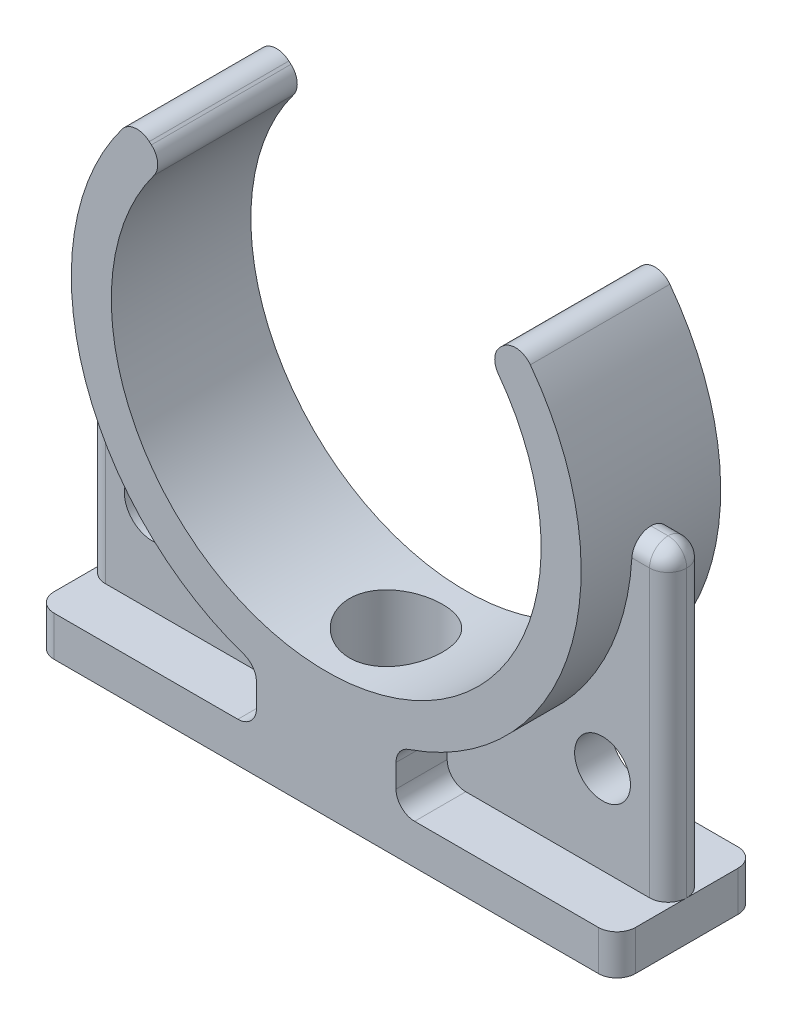
SolidWorks part; units mm, degrees
material "Delrin 2700 NC010, Low Viscosity Acetal Copolymer (SS)"
ref_plane "Front Plane" through (0, 0, 0) normal (0, 0, 1) x (1, 0, 0)
ref_plane "Top Plane" through (0, 0, 0) normal (0, 1, 0) x (1, 0, 0)
ref_plane "Right Plane" through (0, 0, 0) normal (1, 0, 0) x (0, 0, -1)
sketch "Sketch1" plane through (0, 0, 0) normal (0, 0, 1) x (1, 0, 0)
  line L0 (39.6875, 17.145) -> (39.6875, 0) construction
  line L1 (0, 0) -> (79.375, 0)
  line L2 (0, 0) -> (0, 46.99)
  line L3 (0, 46.99) -> (4.8932, 46.99)
  line L4 (79.375, 0) -> (79.375, 46.99)
  line L5 (0, 5.461) -> (30.1625, 5.461)
  line L6 (30.1625, 13.013) -> (30.1625, 5.461)
  line L7 (49.2125, 13.013) -> (49.2125, 5.461)
  line L8 (74.4818, 46.99) -> (79.375, 46.99)
  line L9 (49.2125, 5.461) -> (79.375, 5.461)
  line L10 (13.5513, 69.4559) -> (17.653, 65.8505)
  line L11 (65.8237, 69.4559) -> (61.722, 65.8505)
  circle A0 centre (8.9535, 17.526) radius 3.81
  circle A1 centre (70.4215, 17.526) radius 3.81
  arc A2 (17.653, 65.8505) -> (61.722, 65.8505) centre (39.6875, 46.482) ccw
  arc A3 (49.2125, 13.013) -> (65.8237, 69.4559) centre (39.6875, 46.482) ccw
  arc A4 (13.5513, 69.4559) -> (30.1625, 13.013) centre (39.6875, 46.482) ccw
  point P14 (10.3505, 46.482)
  point P15 (4.8895, 46.482)
  point P16 (39.6875, 17.145)
  point P17 (8.9535, 13.716)
  point P27 (17.653, 65.8505)
  point P28 (61.722, 65.8505)
  dimension "D3" = 61.468
  dimension "D4" = 7.62
  dimension "D5" = 58.674
  dimension "D8" = 13.716
  dimension "D1" = 79.375
  dimension "D2" = 46.99
  dimension "D6" = 5.461
  dimension "D7" = 17.145
  dimension "D9" = 5.461
  dimension "D10" = 19.05
  dimension "D11" = 44.069
extrude "Boss-Extrude1" add sketch "Sketch1" along normal mid plane 19.05 contours A2 L0 L1 L4 L9 L7 A3 L11 | L0 A2 L10 A4 L6 L5 L2 L1 region at (60.1684, 22.8572, 0) region at (19.2066, 22.8572, 0)
extrude "Boss-Extrude2" add sketch "Sketch1<3>" along direction (0, 0, 1) on the side of the normal mid plane 5.08 contours A4 L3 L2 L5 L6 A0 | A3 L7 L9 L4 L8 A1 region at (0.5133, 26.2255, 0) region at (64.2938, 5.9743, 0)
sketch "Sketch1<3>" plane through (0, 0, 0) normal (0, 0, 1) x (1, 0, 0) same geometry as "Sketch1"
fillet "Fillet1" radius 2.54 14 edges at (17.653, 65.8505, 0) (13.5513, 69.4559, 0) (65.8237, 69.4559, 0) (61.722, 65.8505, 0) (76.9284, 46.99, -2.54) (76.9284, 46.99, 2.54) (49.2125, 5.461, 6.0325) (49.2125, 13.013, 6.0325) (79.375, 26.2255, -2.54) (79.375, 26.2255, 2.54) (0, 2.7305, -9.525) (79.375, 2.7305, -9.525) (79.375, 2.7305, 9.525) (0, 2.7305, 9.525)
sketch "Sketch2" plane through (0, 0, 0) normal (0, -1, 0) x (1, 0, 0)
  circle A0 centre (39.6875, 0) radius 2.54
  dimension "D1" = 5.08
extrude "Cut-Extrude1" cut sketch "Sketch2" against normal through all
sketch "Sketch5" plane through (0, 0, 0) normal (0, -1, 0) x (1, 0, 0)
  circle A0 centre (39.6875, 0) radius 6.0325
  dimension "D1" = 12.065
ref_plane "Plane1" through (0, 19.05, 0) normal (0, -1, 0) x (-1, 0, 0)
sketch "Sketch7" plane through (0, 19.05, 0) normal (0, -1, 0) x (-1, 0, 0)
  circle A0 centre (-39.6875, 0) radius 6.35
  dimension "D1" = 12.7
extrude "Cut-Extrude2" cut sketch "Sketch7" along normal blind 18.415
fillet "Fillet2" radius 2.54 6 edges at (30.1625, 13.013, 6.0325) (30.1625, 5.461, 6.0325) (2.4466, 46.99, -2.54) (2.4466, 46.99, 2.54) (0, 26.2255, -2.54) (0, 26.2255, 2.54)
fillet "Fillet3" radius 2.54 4 edges at (30.1625, 5.461, -6.0325) (30.1625, 13.013, -6.0325) (49.2125, 5.461, -6.0325) (49.2125, 13.013, -6.0325)
